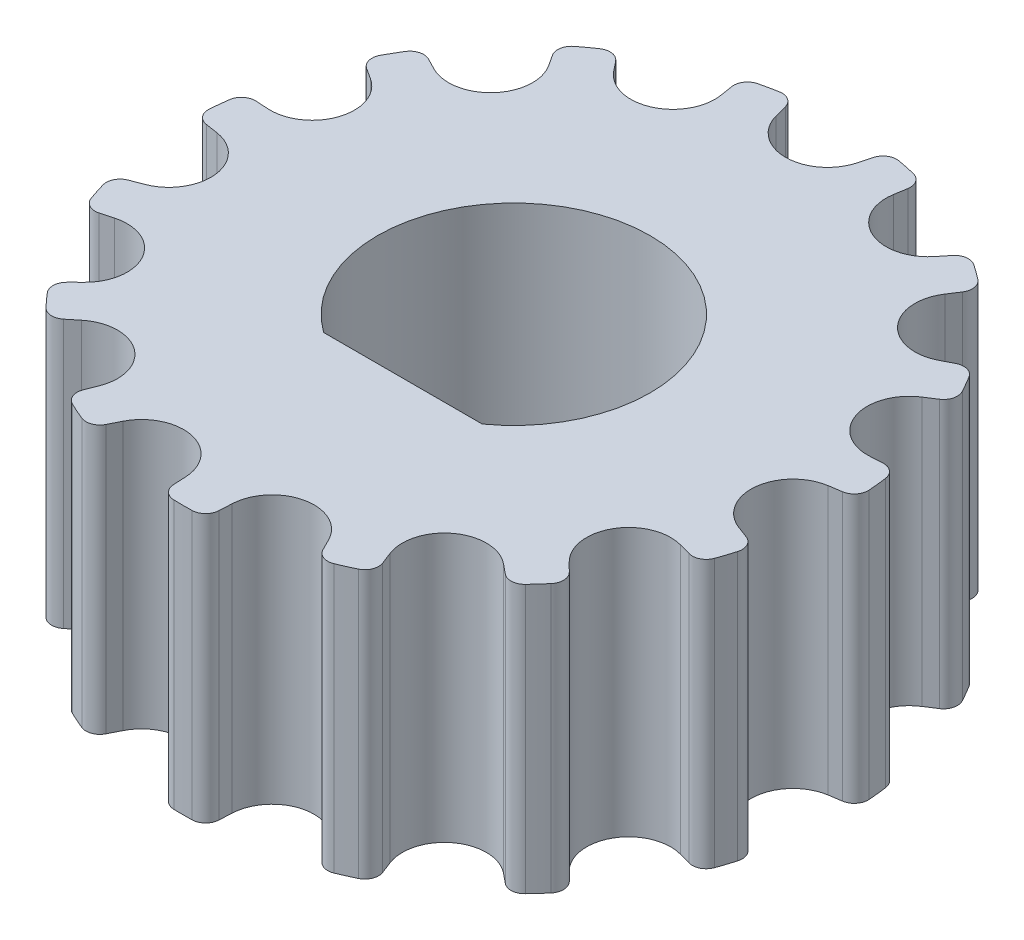
SolidWorks part; units mm, degrees
material "Acrylic (Medium-high impact)"
ref_plane "Front Plane" through (0, 0, 0) normal (0, 0, 1) x (1, 0, 0)
ref_plane "Top Plane" through (0, 0, 0) normal (0, 1, 0) x (1, 0, 0)
ref_plane "Right Plane" through (0, 0, 0) normal (1, 0, 0) x (0, 0, -1)
sketch "Sketch1" plane through (0, 0, 0) normal (0, 1, 0) x (1, 0, 0)
  circle A0 centre (0, 0) radius 7.162
  dimension "D1" = 14.3239
extrude "Boss-Extrude1" add sketch "Sketch1" along normal blind 5.8
sketch "Sketch2" plane through (0, 5.8, 0) normal (0, 1, 0) x (1, 0, 0)
  line L0 (0, 0) -> (0, 7.162) construction
  line L1 (-0.8799, 6.5598) -> (-0.95, 6.8255)
  line L2 (-2.913, 6.5428) -> (-2.913, 7.162)
  line L3 (-2.913, 7.162) -> (2.913, 7.162)
  line L4 (0.8799, 6.5598) -> (0.95, 6.8255)
  line L5 (2.913, 6.5428) -> (2.913, 7.162)
  circle A0 centre (0, 0) radius 7.162 construction
  arc A1 (0.8799, 6.5598) -> (-0.8799, 6.5598) centre (0, 6.792) cw
  arc A2 (-0.95, 6.8255) -> (-1.2943, 7.0441) centre (-1.2401, 6.749) ccw
  arc A4 (0.95, 6.8255) -> (1.2943, 7.0441) centre (1.2401, 6.749) cw
  arc A5 (-1.2943, 7.0441) -> (-2.913, 6.5428) centre (0, 0) ccw
  arc A6 (1.2943, 7.0441) -> (2.913, 6.5428) centre (0, 0) cw
  point P11 (0, 7.162)
  point P19 (0, 5.882)
  dimension "D3" = 0.3
  dimension "D5" = 0.91
  dimension "D2" = 0.95
  dimension "D4" = 1.28
  dimension "D6" = 24
extrude "Cut-Extrude1" cut sketch "Sketch2" against normal through all
pattern_circular "CirPattern1" count 15 over 360 about axis through (0, 5.8, 0) along (0, -1, 0) of "Cut-Extrude1"
sketch "Sketch3" plane through (0, 0, 0) normal (0, -1, 0) x (1, 0, 0)
  line L0 (1.7154, 2.4) -> (-1.7154, 2.4)
  arc A0 (-1.7154, 2.4) -> (1.7154, 2.4) centre (0, 0) ccw
  dimension "D1" = 5.9
  dimension "D2" = 2.4
extrude "Cut-Extrude2" cut sketch "Sketch3" against normal through all
sketch "Sketch5" plane through (0, 0, 0) normal (0, -1, 0) x (1, 0, 0)
  line L60 (5.4179, -3.8244) -> (5.6623, -3.9501)
  line L61 (6.252, -2.9286) -> (6.021, -2.7798)
  line L62 (6.505, -1.2901) -> (6.7794, -1.3055)
  line L63 (6.9027, -0.1325) -> (6.6311, -0.0906)
  line L64 (6.4674, 1.4673) -> (6.7243, 1.5648)
  line L65 (6.3598, 2.6865) -> (6.0946, 2.6144)
  line L66 (5.3115, 3.9709) -> (5.5065, 4.1645)
  line L67 (4.7173, 5.041) -> (4.5044, 4.8673)
  line L68 (3.2371, 5.788) -> (3.3366, 6.0442)
  line L69 (2.2591, 6.5239) -> (2.1352, 6.2786)
  line L70 (0.6031, 6.6042) -> (0.5897, 6.8787)
  line L71 (-0.5897, 6.8787) -> (-0.6031, 6.6042)
  line L72 (-2.1352, 6.2786) -> (-2.2591, 6.5239)
  line L73 (-3.3366, 6.0442) -> (-3.2371, 5.788)
  line L74 (-4.5044, 4.8673) -> (-4.7173, 5.041)
  line L75 (-5.5065, 4.1645) -> (-5.3115, 3.9709)
  line L76 (-6.0946, 2.6144) -> (-6.3598, 2.6865)
  line L77 (-6.7243, 1.5648) -> (-6.4674, 1.4673)
  line L78 (-6.6311, -0.0906) -> (-6.9027, -0.1325)
  line L79 (-6.7794, -1.3055) -> (-6.505, -1.2901)
  line L80 (-6.021, -2.7798) -> (-6.252, -2.9286)
  line L81 (-5.6623, -3.9501) -> (-5.4179, -3.8244)
  line L82 (-4.3698, -4.9885) -> (-4.5203, -5.2184)
  line L83 (-3.5661, -5.9117) -> (-3.394, -5.6974)
  line L84 (-1.963, -6.3345) -> (-2.007, -6.6058)
  line L85 (-0.8533, -6.851) -> (-0.7832, -6.5853)
  line L86 (0.7832, -6.5853) -> (0.8533, -6.851)
  line L87 (2.007, -6.6058) -> (1.963, -6.3345)
  line L88 (3.394, -5.6974) -> (3.5661, -5.9117)
  line L89 (4.5203, -5.2184) -> (4.3698, -4.9885)
  line L90 (5.4179, -3.8244) -> (5.6623, -3.9501)
  line L91 (6.252, -2.9286) -> (6.021, -2.7798)
  line L92 (6.505, -1.2901) -> (6.7794, -1.3055)
  line L93 (6.9027, -0.1325) -> (6.6311, -0.0906)
  line L94 (6.4674, 1.4673) -> (6.7243, 1.5648)
  line L95 (6.3598, 2.6865) -> (6.0946, 2.6144)
  line L96 (5.3115, 3.9709) -> (5.5065, 4.1645)
  line L97 (4.7173, 5.041) -> (4.5044, 4.8673)
  line L98 (3.2371, 5.788) -> (3.3366, 6.0442)
  line L99 (2.2591, 6.5239) -> (2.1352, 6.2786)
  line L100 (0.6031, 6.6042) -> (0.5897, 6.8787)
  line L101 (-0.5897, 6.8787) -> (-0.6031, 6.6042)
  line L102 (-2.1352, 6.2786) -> (-2.2591, 6.5239)
  line L103 (-3.3366, 6.0442) -> (-3.2371, 5.788)
  line L104 (-4.5044, 4.8673) -> (-4.7173, 5.041)
  line L105 (-5.5065, 4.1645) -> (-5.3115, 3.9709)
  line L106 (-6.0946, 2.6144) -> (-6.3598, 2.6865)
  line L107 (-6.7243, 1.5648) -> (-6.4674, 1.4673)
  line L108 (-6.6311, -0.0906) -> (-6.9027, -0.1325)
  line L109 (-6.7794, -1.3055) -> (-6.505, -1.2901)
  line L110 (-6.021, -2.7798) -> (-6.252, -2.9286)
  line L111 (-5.6623, -3.9501) -> (-5.4179, -3.8244)
  line L112 (-4.3698, -4.9885) -> (-4.5203, -5.2184)
  line L113 (-3.5661, -5.9117) -> (-3.394, -5.6974)
  line L114 (-1.963, -6.3345) -> (-2.007, -6.6058)
  line L115 (-0.8533, -6.851) -> (-0.7832, -6.5853)
  line L116 (0.7832, -6.5853) -> (0.8533, -6.851)
  line L117 (2.007, -6.6058) -> (1.963, -6.3345)
  line L118 (3.394, -5.6974) -> (3.5661, -5.9117)
  line L119 (4.5203, -5.2184) -> (4.3698, -4.9885)
  circle A60 centre (0, 0) radius 3.9038
  arc A120 (5.6623, -3.9501) -> (6.186, -3.8039) centre (5.8452, -3.5944) ccw
  arc A121 (6.186, -3.8039) -> (6.3873, -3.4553) centre (0, 0) ccw
  arc A122 (6.3873, -3.4553) -> (6.252, -2.9286) centre (6.0355, -3.2649) ccw
  arc A123 (6.505, -1.2901) -> (6.021, -2.7798) centre (6.4595, -2.0988) ccw
  arc A124 (6.7794, -1.3055) -> (7.1984, -0.959) centre (6.8019, -0.9062) ccw
  arc A125 (7.1984, -0.959) -> (7.2405, -0.5586) centre (0, 0) ccw
  arc A126 (7.2405, -0.5586) -> (6.9027, -0.1325) centre (6.8416, -0.5278) ccw
  arc A127 (6.4674, 1.4673) -> (6.6311, -0.0906) centre (6.7548, 0.71) ccw
  arc A128 (6.7243, 1.5648) -> (6.9661, 2.0518) centre (6.5824, 1.9387) ccw
  arc A129 (6.9661, 2.0518) -> (6.8417, 2.4347) centre (0, 0) ccw
  arc A130 (6.8417, 2.4347) -> (6.3598, 2.6865) centre (6.4648, 2.3006) ccw
  arc A131 (5.3115, 3.9709) -> (6.0946, 2.6144) centre (5.882, 3.396) ccw
  arc A132 (5.5065, 4.1645) -> (5.5293, 4.7077) centre (5.2248, 4.4484) ccw
  arc A133 (5.5293, 4.7077) -> (5.2599, 5.0069) centre (0, 0) ccw
  arc A134 (5.2599, 5.0069) -> (4.7173, 5.041) centre (4.9702, 4.7312) ccw
  arc A135 (3.2371, 5.788) -> (4.5044, 4.8673) centre (3.9922, 5.4948) ccw
  arc A136 (3.3366, 6.0442) -> (3.1365, 6.5497) centre (2.9637, 6.1889) ccw
  arc A137 (3.1365, 6.5497) -> (2.7687, 6.7135) centre (0, 0) ccw
  arc A138 (2.7687, 6.7135) -> (2.2591, 6.5239) centre (2.6162, 6.3437) ccw
  arc A139 (0.6031, 6.6042) -> (2.1352, 6.2786) centre (1.4121, 6.6436) ccw
  arc A140 (0.5897, 6.8787) -> (0.2013, 7.2592) centre (0.1902, 6.8593) ccw
  arc A141 (0.2013, 7.2592) -> (-0.2013, 7.2592) centre (0, 0) ccw
  arc A142 (-0.2013, 7.2592) -> (-0.5897, 6.8787) centre (-0.1902, 6.8593) ccw
  arc A143 (-2.1352, 6.2786) -> (-0.6031, 6.6042) centre (-1.4121, 6.6436) ccw
  arc A144 (-2.2591, 6.5239) -> (-2.7687, 6.7135) centre (-2.6162, 6.3437) ccw
  arc A145 (-2.7687, 6.7135) -> (-3.1365, 6.5497) centre (0, 0) ccw
  arc A146 (-3.1365, 6.5497) -> (-3.3366, 6.0442) centre (-2.9637, 6.1889) ccw
  arc A147 (-4.5044, 4.8673) -> (-3.2371, 5.788) centre (-3.9922, 5.4948) ccw
  arc A148 (-4.7173, 5.041) -> (-5.2599, 5.0069) centre (-4.9702, 4.7312) ccw
  arc A149 (-5.2599, 5.0069) -> (-5.5293, 4.7077) centre (0, 0) ccw
  arc A150 (-5.5293, 4.7077) -> (-5.5065, 4.1645) centre (-5.2248, 4.4484) ccw
  arc A151 (-6.0946, 2.6144) -> (-5.3115, 3.9709) centre (-5.882, 3.396) ccw
  arc A152 (-6.3598, 2.6865) -> (-6.8417, 2.4347) centre (-6.4648, 2.3006) ccw
  arc A153 (-6.8417, 2.4347) -> (-6.9661, 2.0518) centre (0, 0) ccw
  arc A154 (-6.9661, 2.0518) -> (-6.7243, 1.5648) centre (-6.5824, 1.9387) ccw
  arc A155 (-6.6311, -0.0906) -> (-6.4674, 1.4673) centre (-6.7548, 0.71) ccw
  arc A156 (-6.9027, -0.1325) -> (-7.2405, -0.5586) centre (-6.8416, -0.5278) ccw
  arc A157 (-7.2405, -0.5586) -> (-7.1984, -0.959) centre (0, 0) ccw
  arc A158 (-7.1984, -0.959) -> (-6.7794, -1.3055) centre (-6.8019, -0.9062) ccw
  arc A159 (-6.021, -2.7798) -> (-6.505, -1.2901) centre (-6.4595, -2.0988) ccw
  arc A160 (-6.252, -2.9286) -> (-6.3873, -3.4553) centre (-6.0355, -3.2649) ccw
  arc A161 (-6.3873, -3.4553) -> (-6.186, -3.8039) centre (0, 0) ccw
  arc A162 (-6.186, -3.8039) -> (-5.6623, -3.9501) centre (-5.8452, -3.5944) ccw
  arc A163 (-4.3698, -4.9885) -> (-5.4179, -3.8244) centre (-5.0474, -4.5447) ccw
  arc A164 (-4.5203, -5.2184) -> (-4.4297, -5.7545) centre (-4.1857, -5.4375) ccw
  arc A165 (-4.4297, -5.7545) -> (-4.104, -5.9911) centre (0, 0) ccw
  arc A166 (-4.104, -5.9911) -> (-3.5661, -5.9117) centre (-3.8779, -5.6611) ccw
  arc A167 (-1.963, -6.3345) -> (-3.394, -5.6974) centre (-2.7625, -6.2048) ccw
  arc A168 (-2.007, -6.6058) -> (-1.7062, -7.0587) centre (-1.6122, -6.6699) ccw
  arc A169 (-1.7062, -7.0587) -> (-1.3124, -7.1424) centre (0, 0) ccw
  arc A170 (-1.3124, -7.1424) -> (-0.8533, -6.851) centre (-1.2401, -6.749) ccw
  arc A171 (0.7832, -6.5853) -> (-0.7832, -6.5853) centre (0, -6.792) ccw
  arc A172 (0.8533, -6.851) -> (1.3124, -7.1424) centre (1.2401, -6.749) ccw
  arc A173 (1.3124, -7.1424) -> (1.7062, -7.0587) centre (0, 0) ccw
  arc A174 (1.7062, -7.0587) -> (2.007, -6.6058) centre (1.6122, -6.6699) ccw
  arc A175 (3.394, -5.6974) -> (1.963, -6.3345) centre (2.7625, -6.2048) ccw
  arc A176 (3.5661, -5.9117) -> (4.104, -5.9911) centre (3.8779, -5.6611) ccw
  arc A177 (4.104, -5.9911) -> (4.4297, -5.7545) centre (0, 0) ccw
  arc A178 (4.4297, -5.7545) -> (4.5203, -5.2184) centre (4.1857, -5.4375) ccw
  arc A179 (5.4179, -3.8244) -> (4.3698, -4.9885) centre (5.0474, -4.5447) ccw
  arc A180 (5.6623, -3.9501) -> (6.186, -3.8039) centre (5.8452, -3.5944) ccw
  arc A181 (6.186, -3.8039) -> (6.3873, -3.4553) centre (0, 0) ccw
  arc A182 (6.3873, -3.4553) -> (6.252, -2.9286) centre (6.0355, -3.2649) ccw
  arc A183 (6.505, -1.2901) -> (6.021, -2.7798) centre (6.4595, -2.0988) ccw
  arc A184 (6.7794, -1.3055) -> (7.1984, -0.959) centre (6.8019, -0.9062) ccw
  arc A185 (7.1984, -0.959) -> (7.2405, -0.5586) centre (0, 0) ccw
  arc A186 (7.2405, -0.5586) -> (6.9027, -0.1325) centre (6.8416, -0.5278) ccw
  arc A187 (6.4674, 1.4673) -> (6.6311, -0.0906) centre (6.7548, 0.71) ccw
  arc A188 (6.7243, 1.5648) -> (6.9661, 2.0518) centre (6.5824, 1.9387) ccw
  arc A189 (6.9661, 2.0518) -> (6.8417, 2.4347) centre (0, 0) ccw
  arc A190 (6.8417, 2.4347) -> (6.3598, 2.6865) centre (6.4648, 2.3006) ccw
  arc A191 (5.3115, 3.9709) -> (6.0946, 2.6144) centre (5.882, 3.396) ccw
  arc A192 (5.5065, 4.1645) -> (5.5293, 4.7077) centre (5.2248, 4.4484) ccw
  arc A193 (5.5293, 4.7077) -> (5.2599, 5.0069) centre (0, 0) ccw
  arc A194 (5.2599, 5.0069) -> (4.7173, 5.041) centre (4.9702, 4.7312) ccw
  arc A195 (3.2371, 5.788) -> (4.5044, 4.8673) centre (3.9922, 5.4948) ccw
  arc A196 (3.3366, 6.0442) -> (3.1365, 6.5497) centre (2.9637, 6.1889) ccw
  arc A197 (3.1365, 6.5497) -> (2.7687, 6.7135) centre (0, 0) ccw
  arc A198 (2.7687, 6.7135) -> (2.2591, 6.5239) centre (2.6162, 6.3437) ccw
  arc A199 (0.6031, 6.6042) -> (2.1352, 6.2786) centre (1.4121, 6.6436) ccw
  arc A200 (0.5897, 6.8787) -> (0.2013, 7.2592) centre (0.1902, 6.8593) ccw
  arc A201 (0.2013, 7.2592) -> (-0.2013, 7.2592) centre (0, 0) ccw
  arc A202 (-0.2013, 7.2592) -> (-0.5897, 6.8787) centre (-0.1902, 6.8593) ccw
  arc A203 (-2.1352, 6.2786) -> (-0.6031, 6.6042) centre (-1.4121, 6.6436) ccw
  arc A204 (-2.2591, 6.5239) -> (-2.7687, 6.7135) centre (-2.6162, 6.3437) ccw
  arc A205 (-2.7687, 6.7135) -> (-3.1365, 6.5497) centre (0, 0) ccw
  arc A206 (-3.1365, 6.5497) -> (-3.3366, 6.0442) centre (-2.9637, 6.1889) ccw
  arc A207 (-4.5044, 4.8673) -> (-3.2371, 5.788) centre (-3.9922, 5.4948) ccw
  arc A208 (-4.7173, 5.041) -> (-5.2599, 5.0069) centre (-4.9702, 4.7312) ccw
  arc A209 (-5.2599, 5.0069) -> (-5.5293, 4.7077) centre (0, 0) ccw
  arc A210 (-5.5293, 4.7077) -> (-5.5065, 4.1645) centre (-5.2248, 4.4484) ccw
  arc A211 (-6.0946, 2.6144) -> (-5.3115, 3.9709) centre (-5.882, 3.396) ccw
  arc A212 (-6.3598, 2.6865) -> (-6.8417, 2.4347) centre (-6.4648, 2.3006) ccw
  arc A213 (-6.8417, 2.4347) -> (-6.9661, 2.0518) centre (0, 0) ccw
  arc A214 (-6.9661, 2.0518) -> (-6.7243, 1.5648) centre (-6.5824, 1.9387) ccw
  arc A215 (-6.6311, -0.0906) -> (-6.4674, 1.4673) centre (-6.7548, 0.71) ccw
  arc A216 (-6.9027, -0.1325) -> (-7.2405, -0.5586) centre (-6.8416, -0.5278) ccw
  arc A217 (-7.2405, -0.5586) -> (-7.1984, -0.959) centre (0, 0) ccw
  arc A218 (-7.1984, -0.959) -> (-6.7794, -1.3055) centre (-6.8019, -0.9062) ccw
  arc A219 (-6.021, -2.7798) -> (-6.505, -1.2901) centre (-6.4595, -2.0988) ccw
  arc A220 (-6.252, -2.9286) -> (-6.3873, -3.4553) centre (-6.0355, -3.2649) ccw
  arc A221 (-6.3873, -3.4553) -> (-6.186, -3.8039) centre (0, 0) ccw
  arc A222 (-6.186, -3.8039) -> (-5.6623, -3.9501) centre (-5.8452, -3.5944) ccw
  arc A223 (-4.3698, -4.9885) -> (-5.4179, -3.8244) centre (-5.0474, -4.5447) ccw
  arc A224 (-4.5203, -5.2184) -> (-4.4297, -5.7545) centre (-4.1857, -5.4375) ccw
  arc A225 (-4.4297, -5.7545) -> (-4.104, -5.9911) centre (0, 0) ccw
  arc A226 (-4.104, -5.9911) -> (-3.5661, -5.9117) centre (-3.8779, -5.6611) ccw
  arc A227 (-1.963, -6.3345) -> (-3.394, -5.6974) centre (-2.7625, -6.2048) ccw
  arc A228 (-2.007, -6.6058) -> (-1.7062, -7.0587) centre (-1.6122, -6.6699) ccw
  arc A229 (-1.7062, -7.0587) -> (-1.3124, -7.1424) centre (0, 0) ccw
  arc A230 (-1.3124, -7.1424) -> (-0.8533, -6.851) centre (-1.2401, -6.749) ccw
  arc A231 (0.7832, -6.5853) -> (-0.7832, -6.5853) centre (0, -6.792) ccw
  arc A232 (0.8533, -6.851) -> (1.3124, -7.1424) centre (1.2401, -6.749) ccw
  arc A233 (1.3124, -7.1424) -> (1.7062, -7.0587) centre (0, 0) ccw
  arc A234 (1.7062, -7.0587) -> (2.007, -6.6058) centre (1.6122, -6.6699) ccw
  arc A235 (3.394, -5.6974) -> (1.963, -6.3345) centre (2.7625, -6.2048) ccw
  arc A236 (3.5661, -5.9117) -> (4.104, -5.9911) centre (3.8779, -5.6611) ccw
  arc A237 (4.104, -5.9911) -> (4.4297, -5.7545) centre (0, 0) ccw
  arc A238 (4.4297, -5.7545) -> (4.5203, -5.2184) centre (4.1857, -5.4375) ccw
  arc A239 (5.4179, -3.8244) -> (4.3698, -4.9885) centre (5.0474, -4.5447) ccw
  dimension "D1" = 0.1
extrude "Boss-Extrude2" [suppressed] add sketch "Sketch5" against normal up to surface (5.8 mm away) up to face at (0, 5.8, -0.275)
sketch "Sketch6" plane through (0, 5.8, 0) normal (0, 1, 0) x (1, 0, 0)
  circle A0 centre (0, -10) radius 2.5
  dimension "D1" = 5
  dimension "D2" = 10
extrude "Cut-Extrude3" [suppressed] cut sketch "Sketch6" against normal through all
equation "\"smallPulleyTeeth\"= 15"
equation "\"largePulleyTeeth\"= 30"
equation "\"eighthThick\"= 2.9mm"
equation "\"D1@Sketch1\"=3*\"smallPulleyTeeth\"/pi"
equation "\"D1@Boss-Extrude1\" = \"eighthThick\" * 2"
equation "\"D6@Sketch2\"=360/\"smallPulleyTeeth\""
equation "\"quarterThick\"=6.0mm"
equation "\"D1@CirPattern1\"=\"smallPulleyTeeth\""
equation "\"sixteenthThick\" = 1.7mm"
equation "\"OD\" = 145mm"
equation "\"puckAngle\" = 60.5deg"
equation "\"puckDiam\" = 76.5mm"
equation "\"axlePress\" = 5.9mm"
equation "\"press\" = 0.2mm"
equation "\"wheelClear\" = 0.3mm"
equation "\"10-32clear\" = 4.8mm"
equation "\"6-32clear\" = 3.3mm"
equation "\"8-32clear\" = 4.0mm"
equation "\"wheelHeight\" = 22mm"
equation "\"D1@Sketch3\"=\"axlePress\""
